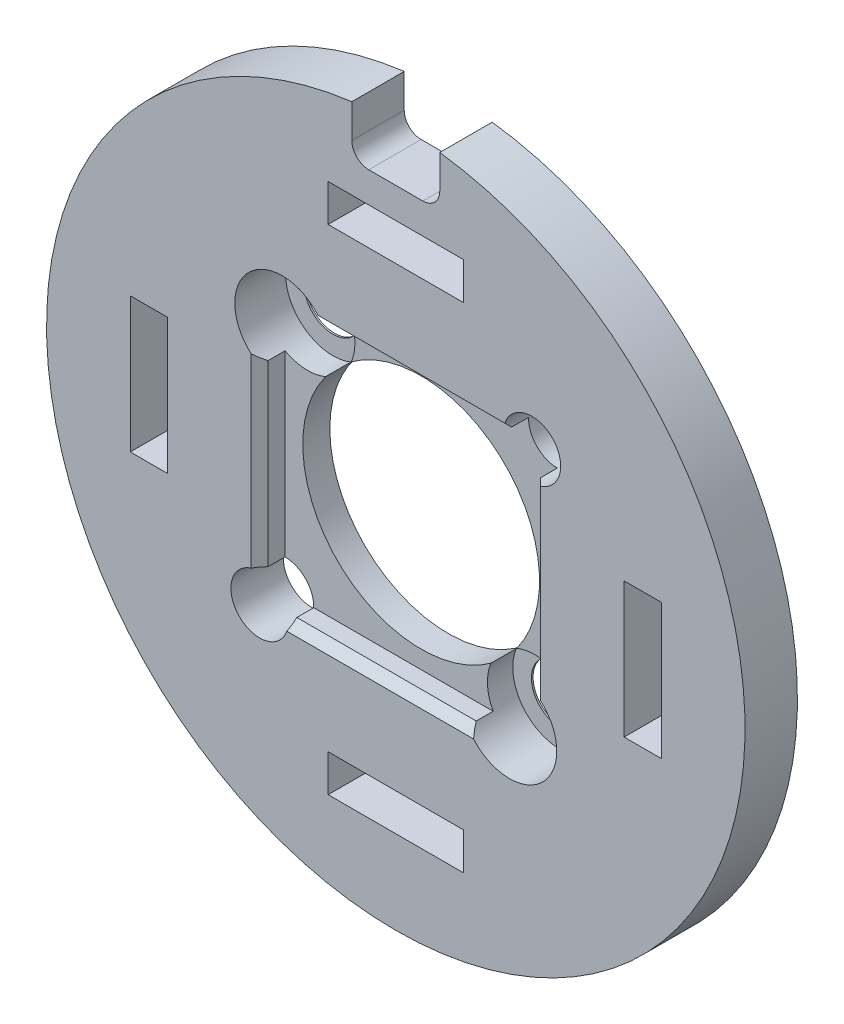
SolidWorks part; units mm, degrees
other "标注1"
sketch "草图10" plane through (17.4, 17.4, 7.6) normal (0.4476, 0.4282, 0.7851) x (0.8625, 0.025, -0.5054)
ref_plane "前视基准面" through (0, 0, 0) normal (0, 0, 1) x (1, 0, 0)
ref_plane "上视基准面" through (0, 0, 0) normal (0, 1, 0) x (1, 0, 0)
ref_plane "右视基准面" through (0, 0, 0) normal (1, 0, 0) x (0, 0, -1)
other "Configuration Table"
sketch "草图1" plane through (0, 0, 0) normal (0, 0, 1) x (1, 0, 0)
  circle A0 centre (0, 0) radius 17.4
  dimension "D1" = 34.8
extrude "凸台-拉伸1" add sketch "草图1" along normal blind 5.6
sketch "草图2" plane through (0, 0, 5.6) normal (0, 0, 1) x (1, 0, 0)
  line L0 (5.5154, -5.5154) -> (6.7175, -6.7175) construction
  line L1 (-6.7175, 6.7175) -> (-5.0175, 6.7175)
  line L2 (-6.7175, 6.7175) -> (-6.7175, 5.0175)
  line L3 (5.0175, -6.7175) -> (6.7175, -6.7175)
  line L4 (6.7175, -5.0175) -> (6.7175, -6.7175)
  line L5 (-6.7175, 6.7175) -> (-0.0325, 0.0325) construction
  line L6 (-6.7175, 6.7175) -> (6.7175, -6.7175)
  circle A0 centre (-6.7175, 6.7175) radius 1.7
  circle A2 centre (6.7175, -6.7175) radius 1.7
  arc A4 (-5.5154, -5.5154) -> (-6.7175, -5.0175) centre (-6.7175, -6.7175) ccw [skipped]
  arc A5 (5.0175, 6.7175) -> (5.5154, 5.5154) centre (6.7175, 6.7175) ccw [skipped]
  point P0 (0, 0)
  point P16 (0, 0)
  dimension "D3" = 3.4
  dimension "D1" = 19
  dimension "D2" = 9.5
  dimension "D4" = 4
extrude "切除-拉伸1" cut sketch "草图2" against normal through all contours A0 | A2
sketch "草图3" plane through (0, 0, 5.6) normal (0, 0, 1) x (1, 0, 0)
  circle A0 centre (0, 0) radius 7
  dimension "D1" = 14
extrude "切除-拉伸2" cut sketch "草图3" against normal through all
sketch "草图4" plane through (0, 0, 5.6) normal (0, 0, 1) x (1, 0, 0)
  circle A1 centre (-6.7175, 6.7175) radius 2.8
  circle A2 centre (6.7175, -6.7175) radius 2.8
  dimension "D1" = 5.6
  dimension "D2" = 5.6
extrude "切除-拉伸3" cut sketch "草图4" against normal blind 3
sketch "草图5" plane through (0, 0, 5.6) normal (0, 0, 1) x (1, 0, 0)
  line L1 (-8.05, 8) -> (8.05, 8)
  line L2 (-8.05, 8) -> (-8.05, -8)
  line L3 (-8.05, -8) -> (8.05, -8)
  line L4 (8.05, 8) -> (8.05, -8)
  line L5 (-8.05, 8) -> (8.05, -8) construction
  line L6 (-8.05, -8) -> (8.05, 8) construction
  circle A0 centre (8.05, 8) radius 1.7
  circle A1 centre (-8.05, -8) radius 1.7
  point P0 (0, 0)
  dimension "D3" = 3.4
  dimension "D4" = 3.4
  dimension "D1" = 16.1
  dimension "D2" = 16
extrude "切除-拉伸4" cut sketch "草图5" against normal through all contours A1 | A0
sketch "草图6" plane through (0, 0, 0) normal (0, 0, -1) x (-1, 0, 0)
  line L0 (4.7668, -8) -> (6.4084, -10.8433)
  line L1 (-4.7668, 8) -> (-6.4084, 10.8433)
  line L2 (-6.4084, 10.8433) -> (-9.6916, 10.8433)
  line L3 (-9.6916, 10.8433) -> (-11.3332, 8)
  line L4 (-11.3332, 8) -> (-9.6916, 5.1567)
  line L5 (-9.6916, 5.1567) -> (-6.4084, 5.1567)
  line L6 (-6.4084, 5.1567) -> (-4.7668, 8)
  line L7 (6.4084, -10.8433) -> (9.6916, -10.8433)
  line L8 (9.6916, -10.8433) -> (11.3332, -8)
  line L9 (11.3332, -8) -> (9.6916, -5.1567)
  line L10 (9.6916, -5.1567) -> (6.4084, -5.1567)
  line L11 (6.4084, -5.1567) -> (4.7668, -8)
  circle A0 centre (-8.05, 8) radius 2.8433 construction
  point P17 (0, 0)
  dimension "D1" = 2
extrude "切除-拉伸5" cut sketch "草图6" against normal blind 2.5
sketch "草图7" plane through (0, 0, 5.6) normal (0, 0, 1) x (1, 0, 0)
  line L5 (-8.05, 8.05) -> (8.05, 8.05)
  line L6 (-8.05, 8.05) -> (-8.05, -8.05)
  line L11 (-8.05, -8.05) -> (8.05, -8.05)
  line L12 (8.05, 8.05) -> (8.05, -8.05)
  line L13 (-8.05, 8.05) -> (8.05, -8.05) construction
  line L14 (-8.05, -8.05) -> (8.05, 8.05) construction
  point P0 (0, 0)
  dimension "D1" = 16.1
  dimension "D2" = 16.1
extrude "切除-拉伸6" cut sketch "草图7" against normal blind 1.5
chamfer "倒角1" distance 0.5 angle 45 4 edges at (1.0479, 8.05, 5.6) (8.05, 1.0226, 5.6) (-1.0479, -8.05, 5.6) (-8.05, -1.0226, 5.6)
sketch "草图8" plane through (0, 0, 0) normal (1, 0, 0) x (0, 0, -1)
  line L0 (0, 17.4) -> (0, 17.2)
  line L1 (0, 17.4) -> (0.2, 17.4)
  line L2 (0.2, 17.4) -> (0, 17.2)
  dimension "D1" = 0.2
  dimension "D2" = 0.2
ref_axis "基准轴1" through (0, 0, 0) along (0, 0, 1)
revolve "旋转1" add sketch "草图8" angle 360 about axis through (0, 0, 0) along (0, 0, 1)
sketch "草图9" plane through (0, 0, 5.6) normal (0, 0, 1) x (1, 0, 0)
  line L0 (0, 0) -> (15, 0) construction
  line L1 (4, -13.5) -> (-4, -13.5)
  line L2 (13.5, 4) -> (16.5, 4)
  line L3 (13.5, 4) -> (13.5, -4)
  line L4 (13.5, -4) -> (16.5, -4)
  line L5 (16.5, 4) -> (16.5, -4)
  line L6 (13.5, 4) -> (16.5, -4) construction
  line L7 (13.5, -4) -> (16.5, 4) construction
  line L8 (4, -13.5) -> (4, -16.5)
  line L9 (4, -16.5) -> (-4, -16.5)
  line L10 (-4, -13.5) -> (-4, -16.5)
  line L11 (-13.5, -4) -> (-13.5, 4)
  line L12 (-13.5, -4) -> (-16.5, -4)
  line L13 (-16.5, -4) -> (-16.5, 4)
  line L14 (-13.5, 4) -> (-16.5, 4)
  line L15 (-4, 13.5) -> (4, 13.5)
  line L16 (-4, 13.5) -> (-4, 16.5)
  line L17 (-4, 16.5) -> (4, 16.5)
  line L18 (4, 13.5) -> (4, 16.5)
  line L19 (15.7, 4) -> (15.7, -4)
  line L20 (4, -15.7) -> (-4, -15.7)
  line L21 (-15.7, -4) -> (-15.7, 4)
  line L22 (-4, 15.7) -> (4, 15.7)
  point P22 (0, 0)
  point P31 (0, 0)
  dimension "D1" = 15
  dimension "D2" = 3
  dimension "D3" = 8
  dimension "D5" = 0.8
  dimension "D4" = 4
  dimension "D6" = 4
extrude "切除-拉伸7" cut sketch "草图9" against normal through all contours L19 L2 L3 L4 | L22 L16 L15 L18 | L21 L12 L11 L14 | L20 L8 L1 L10 region at (0, -14.6, 5.6) region at (14.6, 0, 5.6) region at (-14.6, 0, 5.6) region at (0, 14.6, 5.6)
sketch "Sketch1" plane through (0, 0, 0) normal (0, 0, 1) x (1, 0, 0)
  circle A0 centre (0, 0) radius 17.4
  circle A1 centre (0, 0) radius 20.65
  dimension "D1" = 41.3
extrude "Boss-Extrude1" add sketch "Sketch1" along normal up to surface (5.6 mm away) and the other way blind 4 up to face at (0, 0, 5.6)
sketch "Sketch2" plane through (0, 0, -4) normal (0, 0, -1) x (-1, 0, 0)
  line L0 (0, 0) -> (-17.5, 0)
  line L1 (-17.5, 0) -> (-17.5, 4)
  line L2 (-17.5, 4) -> (-20, 4)
  line L3 (-20, 4) -> (-20, -4)
  line L4 (-20, -4) -> (-17.5, -4)
  line L5 (-17.5, -4) -> (-17.5, 0)
  dimension "D1" = 2.5
  dimension "D2" = 4
  dimension "D3" = 4
  dimension "D4" = 17.5
sketch "Sketch3" plane through (0, 0, -4) normal (0, 0, -1) x (-1, 0, 0)
  circle A0 centre (0, 0) radius 20.65
  circle A1 centre (0, 0) radius 23
  circle M10 centre (0, 0) radius 20.65
  dimension "D1" = 46
extrude "Boss-Extrude2" add sketch "Sketch3" against normal blind 2.5 contours A1 M10 region at (22.3495, 0, -4)
sketch "Sketch4" plane through (0, 0, -4) normal (0, 0, -1) x (-1, 0, 0)
  circle A0 centre (0, 0) radius 18
  dimension "D1" = 36
extrude "Cut-Extrude3" cut sketch "Sketch4" against normal up to surface (4 mm away) up to face at (0, 14.6, 0)
sketch "Sketch5" plane through (0, 0, -4) normal (0, 0, -1) x (-1, 0, 0)
  line L13 (0, 0) -> (23, 0)
  line L14 (0, 0) -> (-23, 0)
  line L15 (23, -4) -> (22, -4)
  line L16 (23, -4) -> (23, 4)
  line L17 (23, 4) -> (22, 4)
  line L18 (22, -4) -> (22, 4)
  line L19 (-23, 4) -> (-22, 4)
  line L20 (-23, 4) -> (-23, -4)
  line L21 (-23, -4) -> (-22, -4)
  line L22 (-22, 4) -> (-22, -4)
  circle A0 centre (0, 0) radius 23 construction
  point P9 (0, 22)
  point P19 (0, -22)
  point P23 (0, 0)
  point P34 (0, 0)
  dimension "D4" = 8
  dimension "D5" = 1
  dimension "D6" = 4
  dimension "D3" = 2
  dimension "D7" = 2
extrude "Cut-Extrude4" cut sketch "Sketch5" against normal blind 10 contours L19 L22 L21 L20 | L16 L15 L18 L17
sketch "Sketch7" plane through (0, 0, -4) normal (0, 0, -1) x (-1, 0, 0)
  line L1 (0, 22.3) -> (2.6, 22.3)
  line L2 (0, 17.5) -> (-2.6, 17.5)
  line L3 (0, 17.5) -> (0, 22.3)
  line L4 (0, 22.3) -> (-2.6, 22.3)
  line L5 (-2.6, 17.5) -> (-2.6, 22.3)
  line L7 (0, 22.3) -> (0, 17.5)
  line L10 (0, 22.3) -> (0, 17.5)
  line L11 (0, 17.5) -> (2.6, 17.5)
  line L12 (2.6, 22.3) -> (2.6, 17.5)
  circle M5 centre (0, 0) radius 18
  dimension "D1" = 2.6
  dimension "D2" = 2.6
  dimension "D3" = 4.8
extrude "Cut-Extrude6" cut sketch "Sketch7" against normal blind 10 contours L5 L3 L4 M5 | L5 L2 L3 M5 | L12 L1 L3 M5 | L12 L3 L11 M5 region at (-1.3094, 20.1182, -4) region at (1.3094, 20.1182, -4) region at (-1.2066, 17.7222, -4) region at (1.2066, 17.7222, -4)
fillet "Fillet3" radius 1 4 edges at (2.6, 22.3, -2.75) (-2.6, 22.3, -2.75) (-2.6, 17.5, 2.8) (2.6, 17.5, 2.8)
sketch "Sketch8" plane through (0, 0, 5.6) normal (0, 0, 1) x (1, 0, 0)
  circle A0 centre (0, 0) radius 23
sketch "Sketch9" plane through (0, 0, -4) normal (0, 0, -1) x (-1, 0, 0)
  circle A0 centre (0, 0) radius 23
extrude "Cut-Extrude8" cut sketch "Sketch9" against normal up to surface (6.5 mm away) up to face at (8.05, 8, 2.5)
